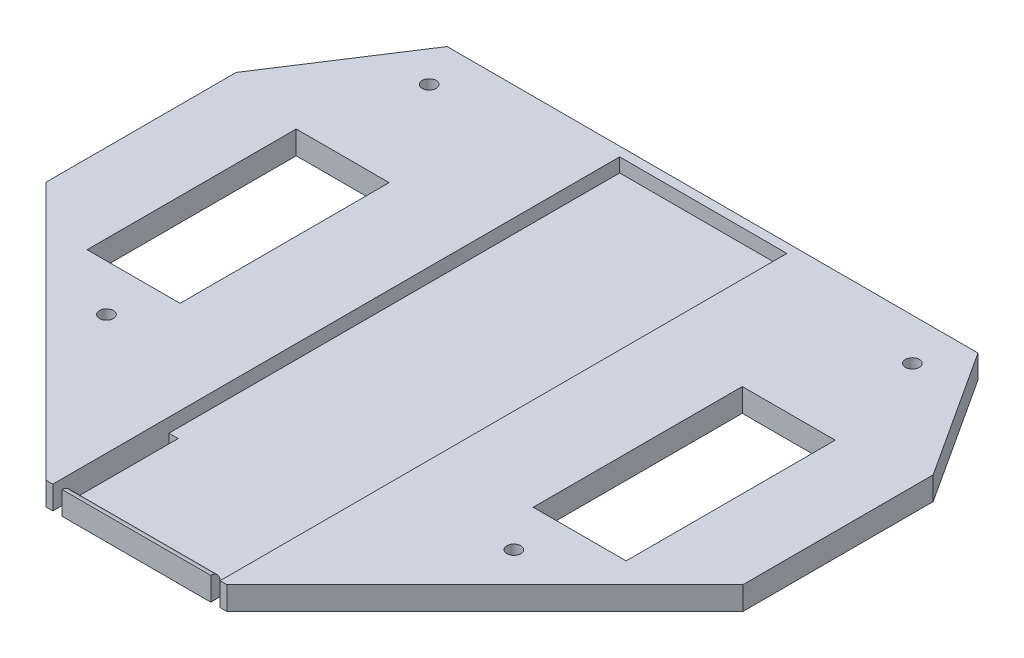
SolidWorks part; units mm, degrees
material "PMMA"
ref_plane "Front Plane" through (0, 0, 0) normal (0, 0, 1) x (1, 0, 0)
ref_plane "Top Plane" through (0, 0, 0) normal (0, 1, 0) x (1, 0, 0)
ref_plane "Right Plane" through (0, 0, 0) normal (1, 0, 0) x (0, 0, -1)
ref_plane "Plane1" through (0, 0, 0) normal (0, 1, 0) x (1, 0, 0)
sketch "Sketch3" plane through (0, 0, 0) normal (0, 1, 0) x (1, 0, 0)
  line L1 (32.541, -115.0018) -> (71.4602, -115.0018)
  line L2 (-23, -59.4608) -> (-23, -18.5314)
  line L3 (-5.122, 8.9982) -> (109.1233, 8.9982)
  line L4 (127, -59.462) -> (127, -18.5295)
  line L5 (109.1233, 8.9982) -> (127, -18.5295)
  line L6 (108.1379, 10.5156) -> (115.3271, -0.5548) construction
  line L7 (-5.122, 8.9982) -> (-23, -18.5314)
  line L8 (-17.9432, -10.7447) -> (2.4807, 20.7055) construction
  line L9 (127, -59.462) -> (71.4602, -115.0018)
  line L10 (52.0006, 8.9982) -> (52.0006, -115.0018) construction
  line L11 (32.541, -115.0018) -> (-23, -59.4608)
  line L12 (95.8412, -77.61) -> (103.9982, -0.0018) construction
  line L13 (103.9982, -0.0018) -> (0, 0) construction
  line L14 (0, 0) -> (8.16, -77.61) construction
  line L15 (8.16, -77.61) -> (95.8412, -77.61) construction
  dimension "D1" = 150
  dimension "D2" = 124
  dimension "D3" = 23
  dimension "D4" = 9
  dimension "D5" = 135
  dimension "D6" = 135
  dimension "D7" = 33
  dimension "D8" = 33
extrude "Boss-Extrude1" add sketch "Sketch3" along normal blind 5
hole_wizard "Ø3.0 (3) Diameter Hole1" positions "Sketch5" profile "Sketch4" hole size "Ø3.0" standard "ANSI Metric"
sketch "Sketch5" plane through (0, 5, 0) normal (0, 1, 0) x (1, 0, 0)
  circle A0 centre (95.8412, -77.61) radius 1.5 construction
  circle A1 centre (8.16, -77.61) radius 1.5 construction
  circle A2 centre (0.003, -0.0018) radius 1.5 construction
  circle A3 centre (103.9982, -0.0018) radius 1.5 construction
  point P30 (95.8412, -77.61)
  point P35 (8.16, -77.61)
  point P40 (103.9982, -0.0018)
  point P45 (0.003, -0.0018)
sketch "Sketch4" plane through (95.8412, 5, 77.61) normal (1, 0, 0) x (0, 0, 1)
  line L0 (0, 0) -> (0, 6.9013)
  line L1 (0, 6.9013) -> (1.5, 6)
  line L2 (1.5, 6) -> (1.5, 0)
  line L5 (1.5, 0) -> (0, 0)
  line L10 (0, 6.9013) -> (-1.5, 6) construction
  line L11 (0, -6.35) -> (0, 107.95) construction
  dimension "Hole Dia." = 3
  dimension "Hole Depth" = 6
  dimension "Drill Angle" = 118
sketch "Sketch6" plane through (0, 5, 0) normal (0, 1, 0) x (1, 0, 0)
  line L0 (-23, -18.5314) -> (-23, -59.4608) construction
  line L1 (34, 6.9982) -> (70, 6.9982)
  line L2 (34, 6.9982) -> (34, -113.0018)
  line L3 (34, -113.0018) -> (70, -113.0018)
  line L4 (70, 6.9982) -> (70, -113.0018)
  line L5 (32.541, -115.0018) -> (71.4602, -115.0018) construction
  dimension "D1" = 120
  dimension "D2" = 36
  dimension "D3" = 57
  dimension "D4" = 2
extrude "Cut-Extrude1" cut sketch "Sketch6" against normal blind 3
sketch "Sketch9" plane through (0, 5, 0) normal (0, 1, 0) x (1, 0, 0)
  line L1 (-6, -22.61) -> (14, -22.61)
  line L2 (-6, -22.61) -> (-6, -67.61)
  line L3 (-6, -67.61) -> (14, -67.61)
  line L4 (14, -22.61) -> (14, -67.61)
  line L5 (34, 6.9982) -> (34, -113.0018) construction
  circle A0 centre (8.16, -77.61) radius 1.5 construction
  dimension "D1" = 45
  dimension "D2" = 10
  dimension "D3" = 20
  dimension "D4" = 20
extrude "Cut-Extrude3" cut sketch "Sketch9" against normal through all
ref_plane "Plane2" through (52, 0, 0) normal (1, 0, 0) x (0, 0, -1)
mirror "Mirror1" about plane through (52, 0, 0) normal (1, 0, 0) of "Cut-Extrude3"
sketch "Sketch10" plane through (0, 5, 0) normal (0, 1, 0) x (1, 0, 0)
  line L0 (34, 6.9982) -> (34, -113.0018) construction
  line L1 (34, -90.0018) -> (36, -90.0018)
  line L2 (34, -90.0018) -> (34, -115.0018)
  line L3 (34, -115.0018) -> (36, -115.0018)
  line L4 (36, -90.0018) -> (36, -115.0018)
  line L5 (32.541, -115.0018) -> (71.4602, -115.0018) construction
  line L6 (70, -113.0018) -> (70, 6.9982) construction
  line L7 (70, -90.0018) -> (68, -90.0018)
  line L8 (70, -90.0018) -> (70, -115.0018)
  line L9 (70, -115.0018) -> (68, -115.0018)
  line L10 (68, -90.0018) -> (68, -115.0018)
  dimension "D1" = 2
  dimension "D2" = 25
  dimension "D3" = 2
  dimension "D4" = 25
extrude "Cut-Extrude4" cut sketch "Sketch10" against normal through all
fillet "Fillet3" radius 2 1 edges at (52, 5, 113.0018)
